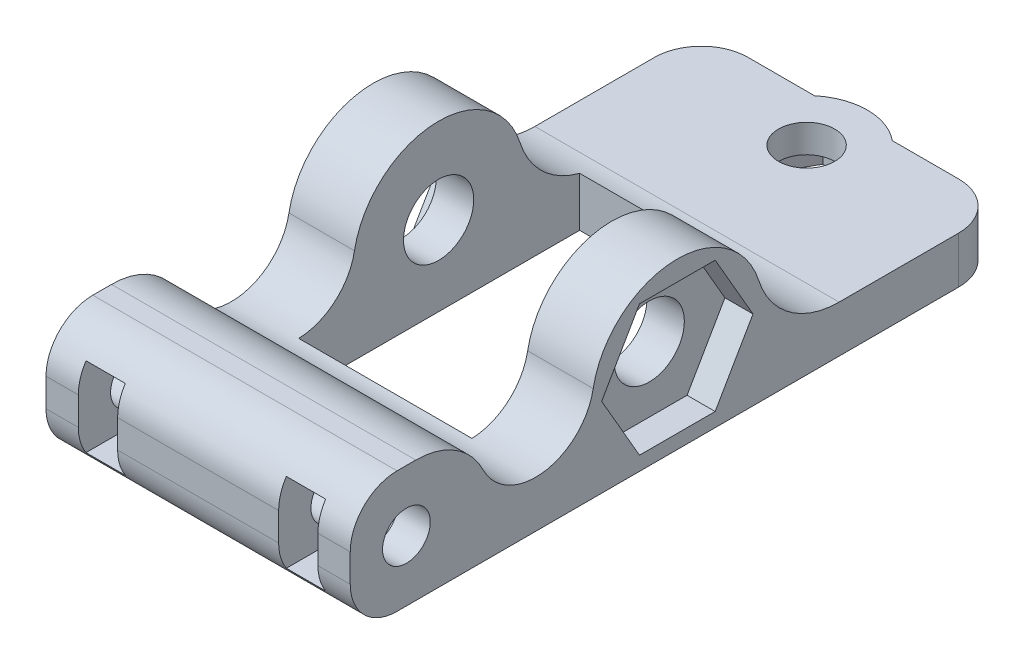
SolidWorks part; units mm, degrees
material "ABS"
ref_plane "Front Plane" through (0, 0, 0) normal (0, 0, 1) x (1, 0, 0)
ref_plane "Top Plane" through (0, 0, 0) normal (0, 1, 0) x (1, 0, 0)
ref_plane "Right Plane" through (0, 0, 0) normal (1, 0, 0) x (0, 0, -1)
sketch "Sketch1" plane through (0, 0, 0) normal (0, 1, 0) x (1, 0, 0)
  line L0 (16.25, 0) -> (16.25, 70) construction
  line L1 (0, 0) -> (32.5, 0)
  line L2 (0, 0) -> (0, 65)
  line L3 (5, 70) -> (27.5, 70) construction
  line L4 (32.5, 0) -> (32.5, 65)
  line L5 (5, 70) -> (12.0967, 70)
  line L6 (20.4033, 70) -> (27.5, 70)
  line L7 (7, 20) -> (7, 50)
  line L8 (7, 20) -> (25.5, 20)
  line L9 (7, 50) -> (25.5, 50)
  line L10 (25.5, 20) -> (25.5, 50)
  line L11 (7, 20) -> (25.5, 50) construction
  line L12 (7, 50) -> (25.5, 20) construction
  arc A0 (27.5, 70) -> (32.5, 65) centre (27.5, 65) cw
  arc A1 (0, 65) -> (5, 70) centre (5, 65) cw
  circle A2 centre (16.25, 65) radius 3
  arc A3 (20.4033, 70) -> (12.0967, 70) centre (16.25, 65) ccw
  point P9 (0, 70)
  point P17 (16.25, 35)
  dimension "D3" = 5
  dimension "D5" = 6
  dimension "D6" = 13
  dimension "D1" = 32.5
  dimension "D2" = 70
  dimension "D4" = 5
  dimension "D7" = 20
  dimension "D8" = 18.5
  dimension "D9" = 30
extrude "Boss-Extrude1" add sketch "Sketch1" along normal blind 18.28
sketch "Sketch2" plane through (0, 0, 0) normal (-1, 0, 0) x (0, 0, 1)
  line L0 (-71.5, 0) -> (-71.5, 5)
  line L1 (-71.5, 18.28) -> (-71.5, 0) construction
  line L2 (-71.5, 5) -> (-52.2203, 5)
  line L3 (-5, 0) -> (-71.5, 0)
  line L4 (-65, 0) -> (0, 0) construction
  line L5 (0, 5) -> (0, 8)
  line L6 (0, 18.28) -> (0, 0) construction
  line L7 (-5, 13) -> (-7, 13)
  line L8 (-52.2203, 5) -> (-52.2487, 5.0162)
  line L9 (-71.5, 5) -> (-71.5, 18.28)
  line L10 (-70, 18.28) -> (-71.5, 18.28) construction
  line L11 (-71.5, 18.28) -> (0, 18.28)
  line L12 (-65, 18.28) -> (0, 18.28) construction
  line L13 (0, 18.28) -> (0, 8)
  circle A0 centre (-34.94, 8.5) radius 3.75
  circle A1 centre (-34.94, 8.5) radius 9.1345
  arc A2 (-43.6442, 11.2704) -> (-52.2203, 5) centre (-52.2203, 14) cw
  arc A3 (-5, 0) -> (0, 5) centre (-5, 5) ccw
  arc A4 (0, 8) -> (-5, 13) centre (-5, 8) ccw
  arc A5 (-7, 13) -> (-14.1898, 8.5081) centre (-7, 5) ccw
  arc A6 (-14.1898, 8.5081) -> (-25.9525, 10.1318) centre (-19.805, 11.248) cw
  circle A7 centre (-6, 6.5) radius 2.55
  point P22 (0, 0)
  point P26 (0, 13)
  point P31 (-19.805, 5)
  line M10 (-65, 0) -> (0, 0)
  line M11 (0, 0) -> (0, 18.28)
  line M12 (0, 18.28) -> (-65, 18.28)
  line M13 (-65, 18.28) -> (-65, 0)
  dimension "D3" = 7.5
  dimension "D4" = 18.2689
  dimension "D5" = 9
  dimension "D6" = 5
  dimension "D8" = 5
  dimension "D9" = 2
  dimension "D10" = 8
  dimension "D11" = 5
  dimension "D12" = 5
  dimension "D13" = 5.1
  dimension "D1" = 3.5
  dimension "D2" = 36.56
  dimension "D7" = 13
  dimension "D14" = 6.5
  dimension "D15" = 6
extrude "Cut-Extrude1" cut sketch "Sketch2" against normal through all contours A6 A5 L7 A4 L2 A2 A1 M11 M12 M13 | L11 L9 L2 M13 | A0 | A3 M10 M11 | A7 region at (0, 11.64, -68.25) region at (0, 11.64, -64.3366) region at (0, 1.1168, -1.1168) region at (0, 8.5, -34.94) region at (0, 6.5, -6)
sketch "Sketch3" plane through (0, 0, 0) normal (-1, 0, 0) x (0, 0, 1)
  line L0 (-65, 0) -> (-5, 0) construction
  line L1 (-26.8571, 8.5) -> (-30.8985, 15.5)
  line L2 (-30.8985, 15.5) -> (-38.9815, 15.5)
  line L3 (-38.9815, 15.5) -> (-43.0229, 8.5)
  line L4 (-43.0229, 8.5) -> (-38.9815, 1.5)
  line L5 (-38.9815, 1.5) -> (-30.8985, 1.5)
  line L6 (-30.8985, 1.5) -> (-26.8571, 8.5)
  circle A0 centre (-34.94, 8.5) radius 7 construction
  dimension "D1" = 14
extrude "Cut-Extrude2" cut sketch "Sketch3" against normal blind 3
ref_plane "Plane1" through (16.25, 0, 0) normal (-1, 0, 0) x (0, 0, 1)
mirror "Mirror1" about plane through (16.25, 0, 0) normal (-1, 0, 0) of "Cut-Extrude2"
sketch "Sketch4" plane through (0, 0, 0) normal (0, 0, 1) x (1, 0, 0)
  line L1 (3.45, 10.75) -> (7.65, 10.75)
  line L2 (3.45, 10.75) -> (3.45, 2.25)
  line L3 (3.45, 2.25) -> (7.65, 2.25)
  line L4 (7.65, 10.75) -> (7.65, 2.25)
  line L5 (3.45, 10.75) -> (7.65, 2.25) construction
  line L6 (3.45, 2.25) -> (7.65, 10.75) construction
  line L7 (0, 8) -> (0, 5) construction
  line L10 (32.5, 0) -> (0, 0) construction
  point P0 (5.55, 6.5)
  dimension "D1" = 8.5
  dimension "D2" = 4.2
  dimension "D3" = 3.45
  dimension "D4" = 6.5
extrude "Cut-Extrude3" cut sketch "Sketch4" against normal blind 11.6758
mirror "Mirror2" about plane through (16.25, 0, 0) normal (-1, 0, 0) of "Cut-Extrude3"
sketch "Sketch5" plane through (0, 0, 0) normal (0, -1, 0) x (1, 0, 0)
  line L0 (27.5, -70) -> (20.4033, -70) construction
  line L1 (11.5157, -65) -> (13.8829, -69.1)
  line L2 (13.8829, -69.1) -> (18.6171, -69.1)
  line L3 (18.6171, -69.1) -> (20.9843, -65)
  line L4 (20.9843, -65) -> (18.6171, -60.9)
  line L5 (18.6171, -60.9) -> (13.8829, -60.9)
  line L6 (13.8829, -60.9) -> (11.5157, -65)
  circle A0 centre (16.25, -65) radius 4.1 construction
  dimension "D1" = 8.2
extrude "Cut-Extrude4" cut sketch "Sketch5" against normal blind 2
